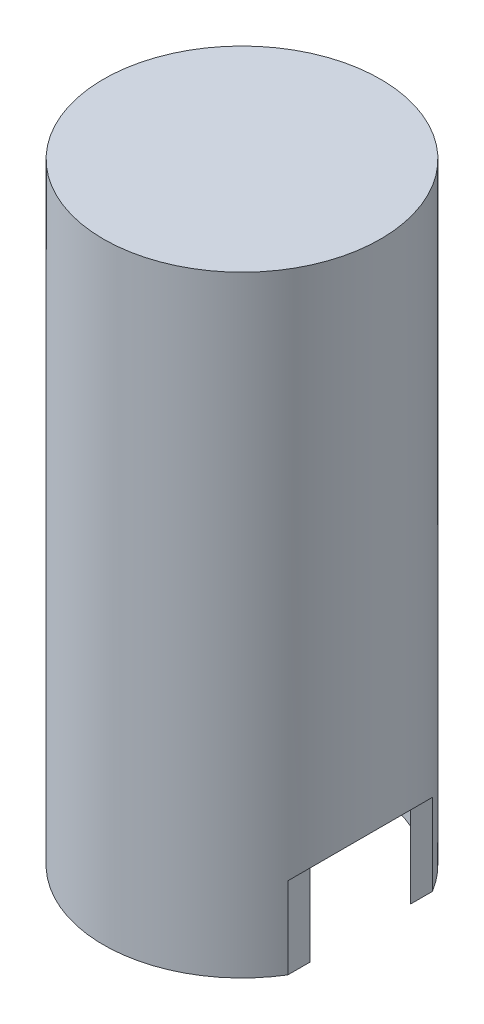
SolidWorks part; units mm, degrees
ref_plane "Front Plane" through (0, 0, 0) normal (0, 0, 1) x (1, 0, 0)
ref_plane "Top Plane" through (0, 0, 0) normal (0, 1, 0) x (1, 0, 0)
ref_plane "Right Plane" through (0, 0, 0) normal (1, 0, 0) x (0, 0, -1)
sketch "Sketch3" plane through (0, 0, 0) normal (0, 1, 0) x (1, 0, 0)
  circle A0 centre (0, 0) radius 68
  dimension "D1" = 136
extrude "Boss-Extrude1" add sketch "Sketch3" along normal blind 300
ref_axis "Axis1" through (0, 300, 0) along (0, -1, 0)
shell "Shell1" thickness 5 removed face at (0, 0, 68)
sketch "Sketch8" plane through (0, 0, 0) normal (0, 0, 1) x (1, 0, 0)
  line L0 (-68, 0) -> (-58, 0)
  line L1 (-68, 0) -> (68, 0) construction
  line L2 (-58, 0) -> (-58, 40)
  line L4 (-68, 300) -> (-68, 0) construction
  line L5 (-68, 50) -> (-68, 0)
  line L6 (-58, 40) -> (-68, 50)
  line L7 (0, -74.8) -> (0, 74.8) construction
  line L8 (68, 0) -> (58, 0)
  line L9 (58, 0) -> (58, 40)
  line L10 (58, 40) -> (68, 50)
  line L11 (68, 50) -> (68, 0)
  point P5 (-54.6305, 45.1253)
  point P10 (-68, 40)
  point P11 (0, 0)
  dimension "D1" = 10
  dimension "D2" = 50
  dimension "D3" = 40
extrude "Cut-Extrude3" cut sketch "Sketch8" against normal through all both and the other way through all
